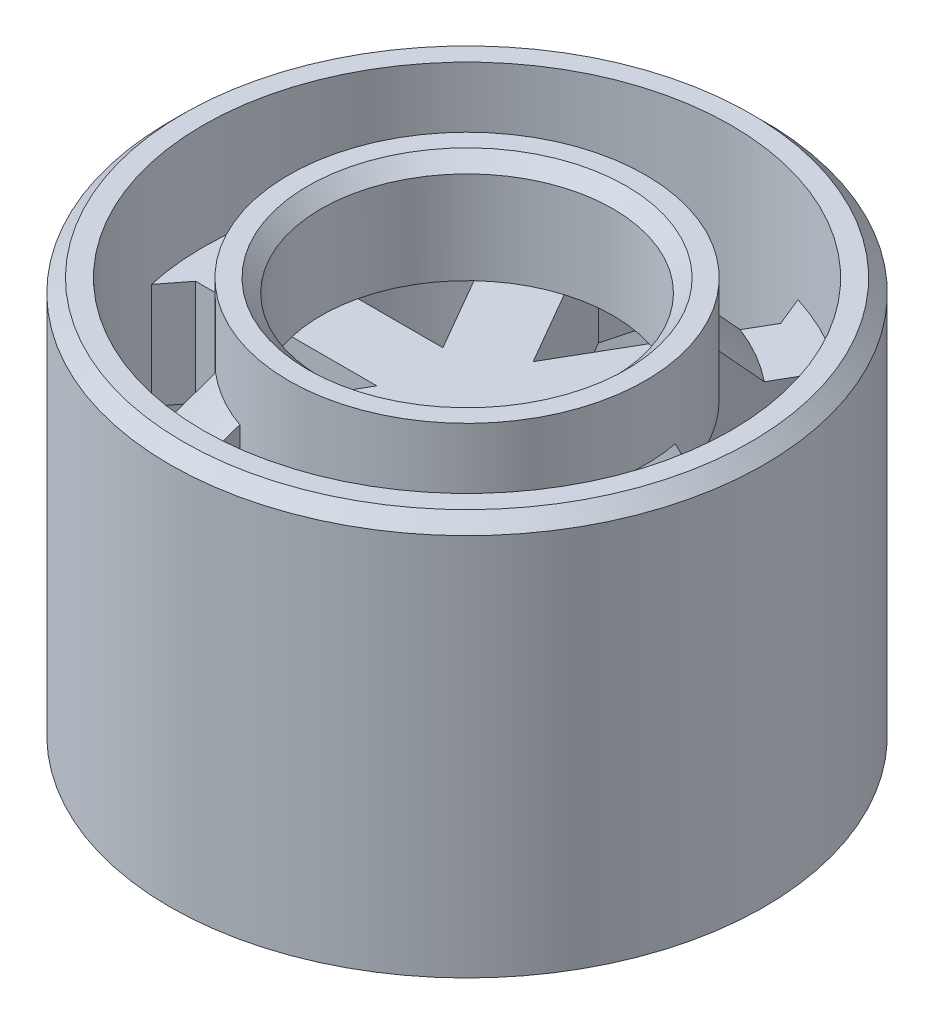
SolidWorks part; units mm, degrees
material "ABS"
ref_plane "Front Plane" through (0, 0, 0) normal (0, 0, 1) x (1, 0, 0)
ref_plane "Top Plane" through (0, 0, 0) normal (0, 1, 0) x (1, 0, 0)
ref_plane "Right Plane" through (0, 0, 0) normal (1, 0, 0) x (0, 0, -1)
sketch "Sketch1" plane through (0, 0, 0) normal (0, 1, 0) x (1, 0, 0)
  circle A0 centre (0, 0) radius 20
  circle A1 centre (0, 0) radius 22.5
  dimension "D1" = 40
  dimension "D2" = 45
extrude "Boss-Extrude1" add sketch "Sketch1" along normal blind 30
ref_plane "Plane1" through (0, 18, 0) normal (0, 1, 0) x (1, 0, 0)
sketch "Sketch2" plane through (0, 18, 0) normal (0, 1, 0) x (1, 0, 0)
  line L0 (-4.3301, 2.5) -> (-12.0866, 15.9347)
  line L1 (0, 5) -> (-7.7565, 18.4347)
  line L2 (0, 5) -> (7.7565, 18.4347)
  line L3 (4.3301, 2.5) -> (12.0866, 15.9347)
  line L4 (4.3301, 2.5) -> (19.8431, 2.5)
  line L5 (4.3301, -2.5) -> (19.8431, -2.5)
  line L6 (4.3301, -2.5) -> (12.0866, -15.9347)
  line L7 (0, -5) -> (7.7565, -18.4347)
  line L8 (0, -5) -> (-7.7565, -18.4347)
  line L9 (-4.3301, -2.5) -> (-12.0866, -15.9347)
  line L10 (-4.3301, -2.5) -> (-19.8431, -2.5)
  line L11 (-4.3301, 2.5) -> (-19.8431, 2.5)
  circle A1 centre (0, 0) radius 5 construction
  circle A2 centre (0, 0) radius 20 construction
  circle A3 centre (0, 0) radius 20
  point P33 (0, 0)
  dimension "D1" = 10
  dimension "D2" = 5
  dimension "D3" = 5
other "Pen Sketch1" parameters "D1"=7.7724, "D2"=2.8749, "D3"=9.1367, "D4"=6
extrude "Boss-Extrude2" add sketch "Sketch2" along normal mid plane 8 contours L7 A3 L6 L5 L4 L3 L2 L1 L0 L11 L10 L9 L8
chamfer "Chamfer1" distance 2 angle 45 12 edges at (-12.0866, 18, 15.9347) (-19.8431, 18, 2.5) (7.7565, 18, 18.4347) (12.0866, 18, 15.9347) (19.8431, 18, -2.5) (-7.7565, 18, 18.4347) (-19.8431, 18, -2.5) (-12.0866, 18, -15.9347) (12.0866, 18, -15.9347) (19.8431, 18, 2.5) (7.7565, 18, -18.4347) (-7.7565, 18, -18.4347)
sketch "Sketch4" plane through (0, 22, 0) normal (0, 1, 0) x (1, 0, 0)
  line L9 (-1.0966, 1.1651) -> (-1.0975, 0.8339)
  line L10 (-1.0975, 0.8339) -> (-1.1024, -0.8274)
  line L11 (-1.1024, -0.8274) -> (-1.1034, -1.1586)
  arc A3 (-1.1034, -1.1586) -> (-1.0966, 1.1651) centre (0, 0) ccw
extrude "Cut-Extrude1" cut sketch "Sketch4" against normal through all both and the other way through all
sketch "Sketch5" plane through (0, 22, 0) normal (0, 1, 0) x (1, 0, 0)
  line L2 (-1.0966, 1.1651) -> (-1.1034, -1.1586) construction
  line L3 (-1.0966, 1.1651) -> (-1.1034, -1.1586)
  arc A2 (-1.1034, -1.1586) -> (-1.0966, 1.1651) centre (0, 0) ccw construction
  arc A3 (-1.1034, -1.1586) -> (-1.0966, 1.1651) centre (0, 0) ccw
  point P6 (0, 0)
extrude "Boss-Extrude3" add sketch "Sketch5" against normal blind 1.5
sketch "Sketch6" plane through (0, 22, 0) normal (0, 1, 0) x (1, 0, 0)
  circle A0 centre (0, 0) radius 11.05
  circle A1 centre (0, 0) radius 13.5
  dimension "D1" = 22.1
  dimension "D2" = 27
extrude "Boss-Extrude4" add sketch "Sketch6" along normal up to surface (8 mm away) up to face at (0, 30, 22.5)
chamfer "Chamfer2" distance 1 angle 45 1 edges at (0, 30, 22.5)
chamfer "Chamfer3" distance 1 angle 45 1 edges at (0, 30, 11.05)
chamfer "Chamfer4" distance 2.5 angle 45 6 edges at (-6.75, 22, 11.6913) (-13.5, 22, 0) (-6.75, 22, -11.6913) (6.75, 22, 11.6913) (13.5, 22, 0) (6.75, 22, -11.6913)
